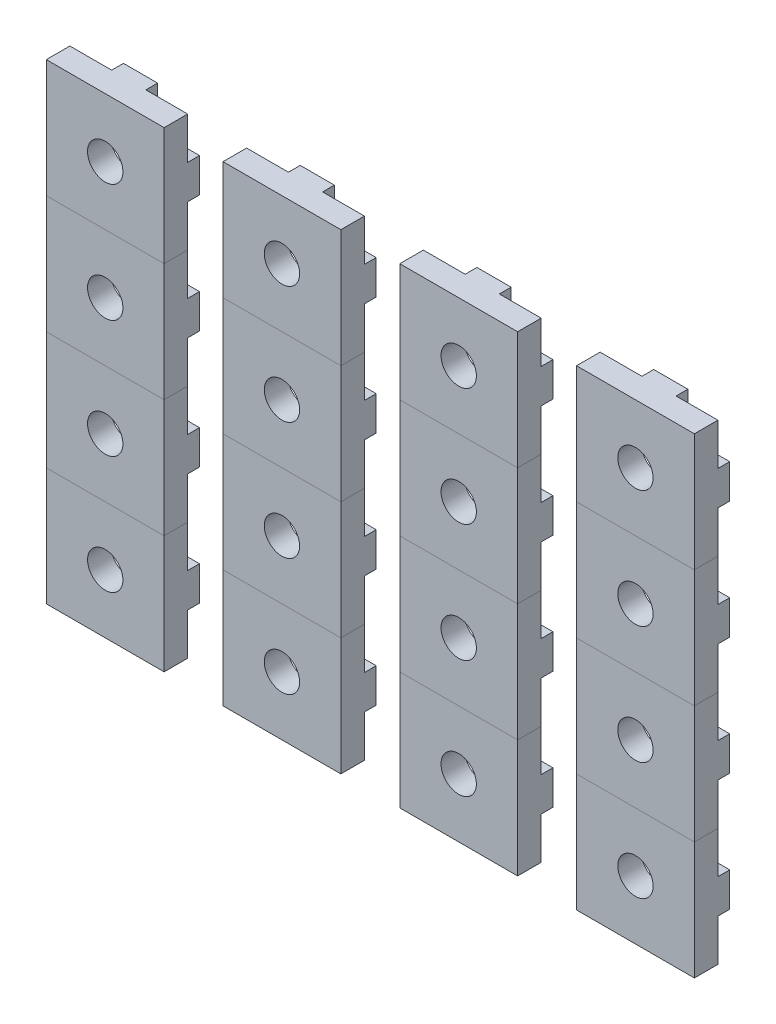
SolidWorks part; units mm, degrees
note: '?' marks a value the reader was unsure of.
ref_plane "Front Plane" through (0, 0, 0) normal (0, 0, 1) x (1, 0, 0)
ref_plane "Top Plane" through (0, 0, 0) normal (0, 1, 0) x (1, 0, 0)
ref_plane "Right Plane" through (0, 0, 0) normal (1, 0, 0) x (0, 0, -1)
ref_axis "Axis1" through (0, 0, -1.2) along (0, 0, 1)?
sketch "Sketch1" plane through (0, 0, 0) normal (0, 0, 1) x (1, 0, 0)
  line L1 (-5, -5) -> (5, -5)
  line L2 (-5, -5) -> (-5, 5)
  line L3 (-5, 5) -> (5, 5)
  line L4 (5, -5) -> (5, 5)
  line L5 (-5, -5) -> (5, 5) construction
  line L6 (-5, 5) -> (5, -5) construction
  circle A0 centre (0, 0) radius 1.5
  point P0 (0, 0)
  dimension "D3" = 3
  dimension "D1" = 10
  dimension "D2" = 10
extrude "Main" add sketch "Sketch1" along normal blind 2
sketch "Sketch2" plane through (0, 0, 0) normal (0, 0, -1) x (-1, 0, 0)
  line L0 (-5, 1.45) -> (-3.9, 1.45)
  line L1 (-5, -5) -> (-5, 5) construction
  line L2 (-3.9, 1.45) -> (-3.9, 3)
  line L3 (-3.9, -1.45) -> (-5, -1.45)
  line L4 (-5, 1.45) -> (-5, -1.45)
  line L5 (-3.9, 3) -> (-2.1, 0.95)
  line L6 (-2.1, 0.95) -> (-2.1, -0.95)
  line L7 (-2.1, -0.95) -> (-3.9, -3)
  line L8 (-3.9, -3) -> (-3.9, -1.45)
  line L9 (-5, 5) -> (5, 5) construction
  point P5 (-2.1, 0)
  dimension "D1" = 2.9
  dimension "D2" = 1.1
  dimension "D3" = 1.9
  dimension "D4" = 2.1
  dimension "D5" = 2
extrude "AntiRotationSystem" add sketch "Sketch2" along normal blind 1
pattern_circular "CirPattern1" count 4 over 360 about axis through (0, 0, 0) along (0, 0, 1) of "AntiRotationSystem"
pattern_linear "LPattern1" count 4 spacing 10 along (0, -1, 0) of bodies 103
pattern_linear "LPattern2" count 4 spacing 15 along (-1, 0, 0) of bodies 103 107 110 112
